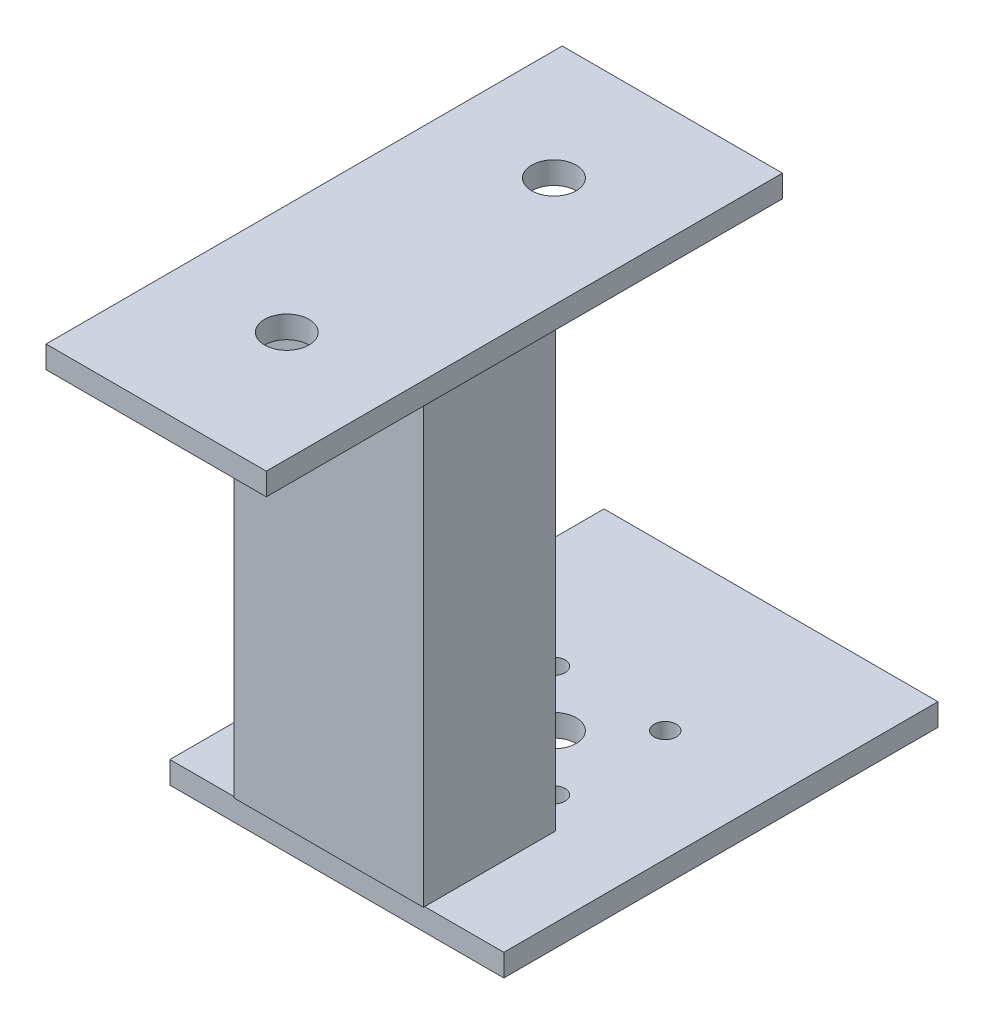
SolidWorks part; units mm, degrees
ref_plane "Front Plane" through (0, 0, 0) normal (0, 0, 1) x (1, 0, 0)
ref_plane "Top Plane" through (0, 0, 0) normal (0, 1, 0) x (1, 0, 0)
ref_plane "Right Plane" through (0, 0, 0) normal (1, 0, 0) x (0, 0, -1)
sketch "草图1" plane through (0, 0, 0) normal (0, 1, 0) x (1, 0, 0)
  line L0 (-5.75, 19.5) -> (24.25, 19.5)
  line L1 (0, 0) -> (24.25, 0)
  line L3 (0, 39) -> (24.25, 39)
  line L4 (24.25, 0) -> (24.25, 39)
  line L5 (0, 0) -> (-5.75, 0)
  line L6 (-5.75, 0) -> (-5.75, 39)
  line L7 (-5.75, 39) -> (0, 39)
  line L8 (9.25, 19.5) -> (9.25, 14.5)
  line L9 (9.25, 14.5) -> (14.25, 14.5)
  circle A1 centre (9.25, 19.5) radius 2
  circle A2 centre (14.25, 14.5) radius 1
  circle A3 centre (4.25, 14.5) radius 1
  circle A4 centre (4.25, 24.5) radius 1
  circle A5 centre (14.25, 24.5) radius 1
  dimension "D1" = 4
extrude "凸台-拉伸1" add sketch "草图1" along normal blind 2 contours A1 L0 L4 L3 | A1 L0 L1 L4 region at (9.25, 0, -29.3998) region at (9.25, 0, -9.6002)
sketch "草图2" plane through (0, 2, 0) normal (0, 1, 0) x (1, 0, 0)
  line L0 (0.1133, 11.777) -> (17.1359, 11.777)
  line L6 (17.1359, -0.1156) -> (17.1359, 11.777)
  line L19 (9.25, 19.5) -> (3.1643, 19.5)
  line L20 (0.1133, -0.1156) -> (17.1359, -0.1156)
  line L21 (0.1133, -0.1156) -> (0.1133, 11.777)
extrude "凸台-拉伸2" add sketch "草图2" along normal blind 43 contours L21 L20 L6 L0 region at (8.6246, 2, -5.8307)
sketch "草图3" plane through (0, 45, 0) normal (0, 1, 0) x (1, 0, 0)
  line L0 (-0.6431, -16.2352) -> (19.1431, -16.2352)
  line L1 (9.25, 19.5) -> (9.25, 25.4855)
  line L2 (9.25, 43.5) -> (9.25, 50.3507)
  line L19 (9.25, 41.5) -> (9.25, 43.5)
  line L30 (-0.6431, 50.3507) -> (19.1431, 50.3507)
  line L31 (19.1431, 30.1381) -> (-0.6431, 30.1381)
  line L37 (19.1431, -16.2352) -> (19.1431, 30.1381)
  line L38 (-0.6431, -16.2352) -> (-0.6431, 30.1381)
  circle A1 centre (9.25, -4.5) radius 2
  circle A2 centre (9.25, 19.5) radius 2
  circle A4 centre (9.25, 43.5) radius 2
extrude "凸台-拉伸3" add sketch "草图3" against normal blind 2 contours A4 A2 A1 region at (9.25, 45, -6.936)
